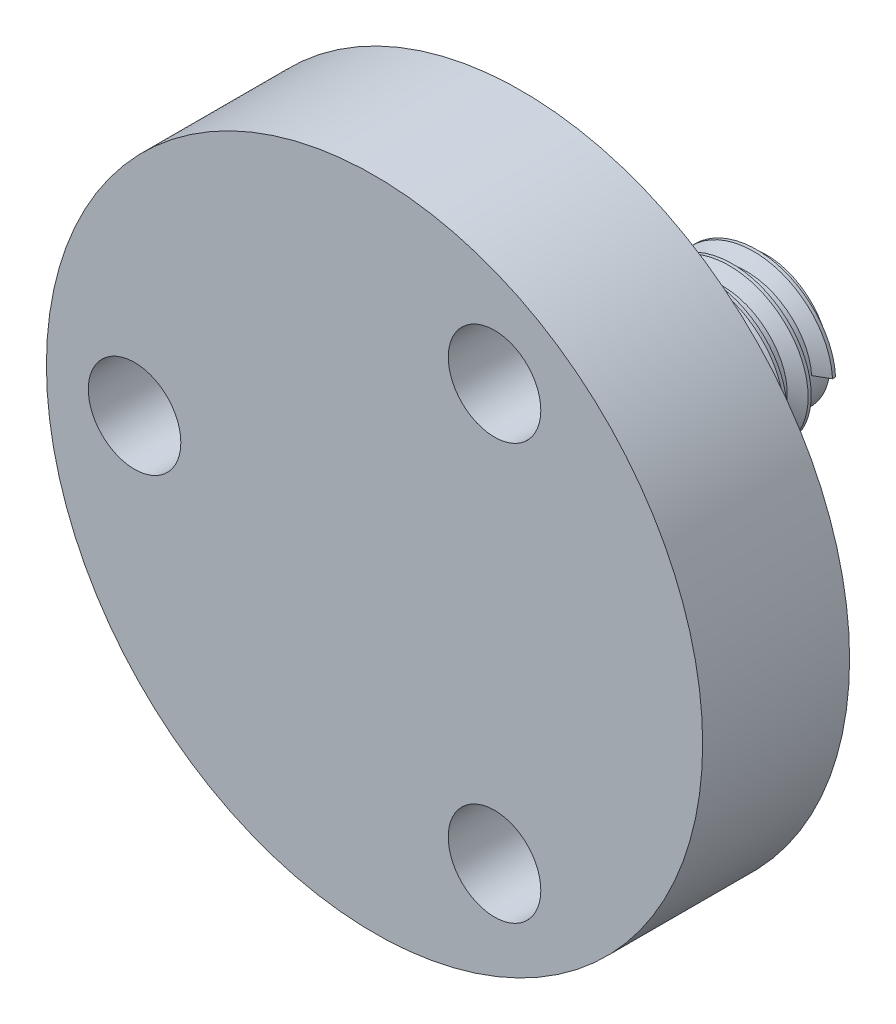
SolidWorks part; units mm, degrees
ref_plane "Front Plane" through (0, 0, 0) normal (0, 0, 1) x (1, 0, 0)
ref_plane "Top Plane" through (0, 0, 0) normal (0, 1, 0) x (1, 0, 0)
ref_plane "Right Plane" through (0, 0, 0) normal (1, 0, 0) x (0, 0, -1)
sketch "Sketch2" plane through (0, 0, 0) normal (0, 0, 1) x (1, 0, 0)
  circle A0 centre (0, 0) radius 8.509
  dimension "D1" = 17.018
extrude "Boss-Extrude1" add sketch "Sketch2" along normal blind 3.81
ref_plane "Plane1" through (0, 0, 3.81) normal (0, 0, 1) x (1, 0, 0)
sketch "Sketch3" plane through (0, 0, 3.81) normal (0, 0, 1) x (1, 0, 0)
  line L0 (-8.509, 0) -> (8.509, 0) construction
  circle A0 centre (0, 0) radius 6.223 construction
  circle A2 centre (0, 0) radius 8.509 construction
  circle A3 centre (-6.223, 0) radius 1.143
  circle A4 centre (3.1115, 5.3893) radius 1.143
  circle A5 centre (3.1115, -5.3893) radius 1.143
  point P16 (0, 0)
  dimension "D1" = 12.446
  dimension "D2" = 2.286
  dimension "D4" = 5.3893
  dimension "D5" = 3.1115
  dimension "D3" = 3
hole_wizard "M2 Clearance Hole1" positions "Sketch6" profile "Sketch7" hole size "M2" standard "ANSI Metric" end condition through all
sketch "Sketch6" plane through (0, 0, 3.81) normal (0, 0, 1) x (1, 0, 0)
  point P0 (-6.223, 0)
  point P3 (3.1115, 5.3893)
  point P6 (3.1115, -5.3893)
sketch "Sketch7" plane through (-6.223, 0, 3.81) normal (1, 0, 0) x (0, -1, 0)
  line L0 (0, 0) -> (0, 3.81)
  line L1 (0, 3.81) -> (1.2, 3.81)
  line L2 (1.2, 3.81) -> (1.2, 0)
  line L5 (1.2, 0) -> (0, 0)
  line L11 (0, -6.35) -> (0, 107.95) construction
  dimension "Thru Hole Dia." = 2.4
  dimension "Thru Hole Depth" = 3.81
sketch "Sketch8" plane through (0, 0, 0) normal (0, 0, -1) x (-1, 0, 0)
  circle A1 centre (0, 0) radius 1.651
  point P0 (0, 0)
  dimension "D1" = 3.302
extrude "Boss-Extrude2" add sketch "Sketch8" along normal blind 6.35
thread "Thread1" pitch 0.635 method extrude profile "Thread Profile2" start angle 0, offset 0, length 0, pitch 0.635, diameter 3.302
ref_plane "Plane3" through (1.651, 0, -6.35) normal (0, -1, 0) x (1, 0, 0)
sketch "Thread Profile2" plane through (1.651, 0, -6.35) normal (0, -1, 0) x (1, 0, 0)
  line L0 (0, 0) -> (0, 0.635) construction
  line L1 (0, 0) -> (0.3437, 0.1984)
  line L2 (0.3437, 0.1984) -> (0.3437, 0.2778)
  line L3 (0.3437, 0.2778) -> (0, 0.4762)
  line L4 (0.3437, 0.2381) -> (0, 0.2381) construction
  line L11 (0, 0) -> (0, 0.4762)
  point P2 (0, 0)
  dimension "Pitch" = 0.635
  dimension "Profile_Angle" = 60
  dimension "Profile_Land" = 0.0794
  dimension "Profile_Height" = 0.3437
chamfer "Chamfer1" distance 0.75 angle 45 3 edges at (4.3115, -5.3893, 0) (4.3115, 5.3893, 0) (-5.023, 0, 0)
